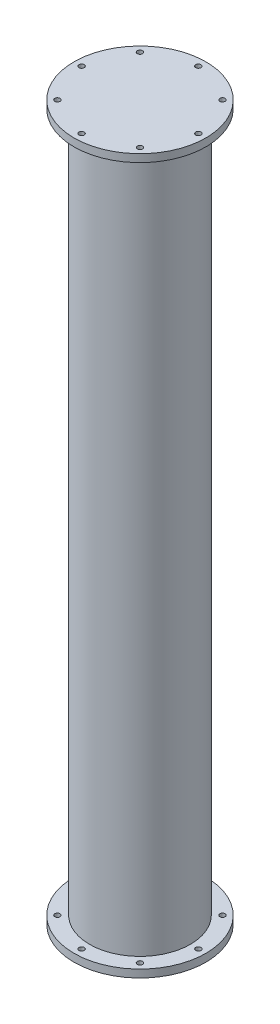
SolidWorks part; units mm, degrees
material "7075-O (SS)"
ref_plane "Front" through (0, 0, 0) normal (0, 0, 1) x (1, 0, 0)
ref_plane "Top" through (0, 0, 0) normal (0, 1, 0) x (1, 0, 0)
ref_plane "Right" through (0, 0, 0) normal (1, 0, 0) x (0, 0, -1)
sketch "Croquis1" plane through (0, 0, 0) normal (0, 1, 0) x (1, 0, 0)
  circle A0 centre (0, 0) radius 32.5
  circle A1 centre (0, 0) radius 30
  dimension "DE" = 65
  dimension "DI" = 60
extrude "Saliente-Extruir1" add sketch "Croquis1" along normal mid plane 450
sketch "Croquis2" plane through (0, 225, 0) normal (0, 1, 0) x (1, 0, 0)
  line L0 (0, 42.5) -> (0, 32.7) construction
  circle A0 centre (0, 0) radius 42.5
  dimension "D1" = 85
extrude "Saliente-Extruir2" add sketch "Croquis2" along normal blind 5
hole_wizard "Taladro de margen para M31" positions "Croquis3" profile "Croquis4" hole size "M3" standard "Ansi Metric" end condition up to next
sketch "Croquis3" plane through (0, 225, 0) normal (0, -1, 0) x (-1, 0, 0)
  line L0 (0, -42.5) -> (0, -32.7) construction
  line L1 (0, 50) -> (0, -50) construction
  line L2 (0, 32.7) -> (0, 42.5) construction
  circle A0 centre (0, 0) radius 32.7 construction
  circle A1 centre (0, 0) radius 42.5 construction
  point P13 (-26.5872, -26.5872)
  point P21 (-37.6, 0)
  point P22 (-26.5872, 26.5872)
  point P23 (0, 37.6)
  point P24 (26.5872, 26.5872)
  point P25 (37.6, 0)
  point P34 (26.5872, -26.5872)
  point P35 (0, -37.6)
  point P37 (0, 0)
  point P38 (0, 0)
  dimension "D1" = 65.4
  dimension "D2" = 8
sketch "Croquis4" plane through (0, 225, 37.6) normal (1, 0, 0) x (0, 0, -1)
  line L0 (0, 0) -> (0, 5.001)
  line L1 (0, 5.001) -> (1.7, 5.001)
  line L2 (1.7, 5.001) -> (1.7, 0)
  line L5 (1.7, 0) -> (0, 0)
  line L11 (0, -6.35) -> (0, 107.95) construction
  dimension "Diámetro de taladro hasta el siguiente" = 3.4
  dimension "Profundidad de taladro hasta el siguiente" = 5.001
mirror "Simetría1" about plane through (0, 0, 0) normal (0, 1, 0) of "Taladro de margen para M31", "Saliente-Extruir2"
